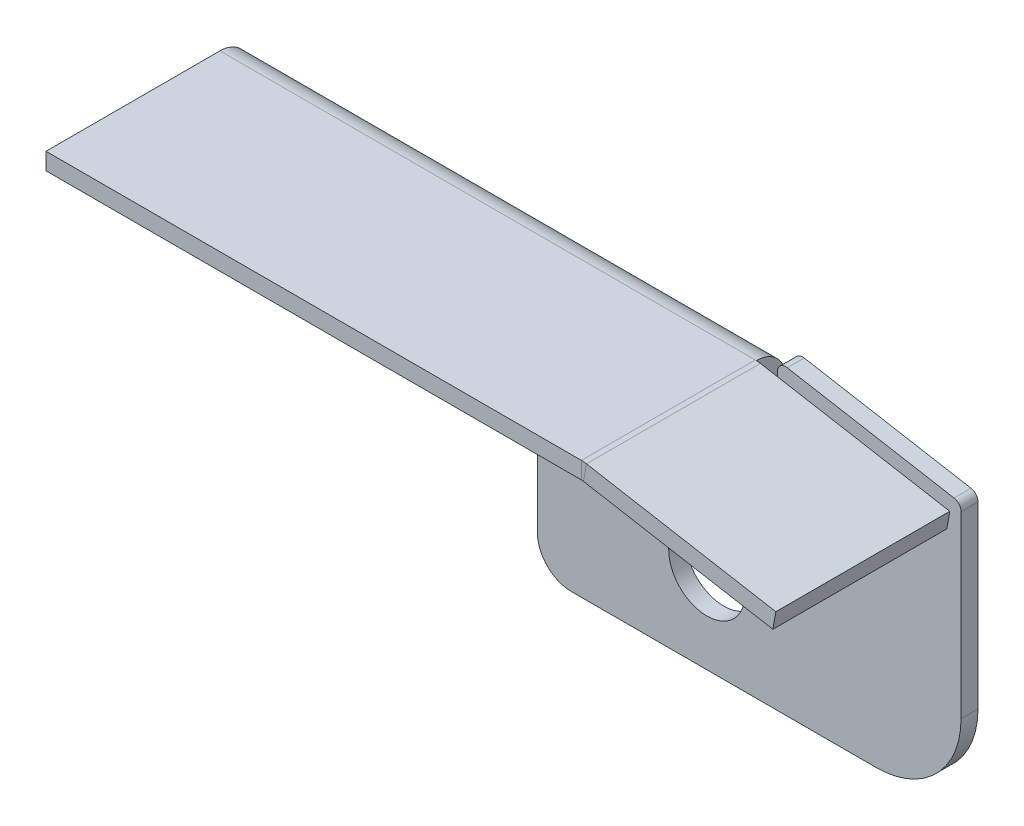
SolidWorks part; units mm, degrees
note: The reader was unsure of these and kept them because the rebuilt part matched: flange length of "Kante-Lasche1", "Kante-Lasche2".
material "1.4301 (X5CrNi18-10)"
ref_plane "Ebene vorne" through (0, 0, 0) normal (0, 0, 1) x (1, 0, 0)
ref_plane "Ebene oben" through (0, 0, 0) normal (0, 1, 0) x (1, 0, 0)
ref_plane "Ebene rechts" through (0, 0, 0) normal (1, 0, 0) x (0, 0, -1)
sketch "Skizze1" plane through (0, 0, 0) normal (0, 0, 1) x (1, 0, 0)
  line L0 (-42, -8.5) -> (-42, -16.5)
  line L1 (-40, -18.5) -> (-22, -18.5)
  line L2 (-17, -13.5) -> (-17, -2.5)
  line L3 (-17, -2.5) -> (-28.3426, -0.5)
  line L4 (-28.3426, -0.5) -> (-60, -0.5)
  line L5 (-42, 58) -> (-42, -58) construction
  line L6 (-32, -7.5) -> (-32, -13.5) construction
  line L7 (-29.75, -7.5) -> (-29.75, -13.5)
  line L8 (-34.25, -7.5) -> (-34.25, -13.5)
  line L9 (-42, -8.5) -> (-58, -8.5)
  line L10 (-60, 53) -> (-60, -53) construction
  line L12 (-60, 50) -> (-60, -50) construction
  line L13 (-60, -6.5) -> (-60, -0.5)
  arc A0 (-29.75, -7.5) -> (-34.25, -7.5) centre (-32, -7.5) ccw
  arc A1 (-34.25, -13.5) -> (-29.75, -13.5) centre (-32, -13.5) ccw
  arc A2 (-17, -13.5) -> (-22, -18.5) centre (-22, -13.5) cw
  arc A3 (-42, -16.5) -> (-40, -18.5) centre (-40, -16.5) ccw
  arc A4 (-58, -8.5) -> (-60, -6.5) centre (-58, -6.5) cw
  point P7 (-32, -10.5)
  point P26 (-17, -18.5)
  point P31 (-60, -8.5)
  dimension "D10" = 5
  dimension "D11" = 2
  dimension "D12" = 2
  dimension "D1" = 18
  dimension "D2" = 25
  dimension "D3" = 100
  dimension "D4" = 0.5
  dimension "D5" = 16
  dimension "D6" = 4.5
  dimension "D7" = 6
  dimension "D8" = 8
  dimension "D9" = 8
base flange "Basis-Blech1" sketch "Skizze1" thickness 1 reverse thickness direction yes parameters "D1"=0.7366
edge flange "Kante-Lasche1" sketch "Skizze11" flange angle 90 flange length 12 flange position material inside bend radius 0.7366 thickness 1 relief rectangular parameters "D6"=10, "D8"=1
sketch "Skizze11" plane through (0, -0.5, 1) normal (0, 1, 0) x (-1, 0, 0)
  line L2 (28.3426, 0) -> (28.3426, 11)
  line L3 (28.3426, 11) -> (60, 11)
  line L4 (60, 11) -> (60, 0)
  line L7 (28.3426, 0) -> (60, 0) construction
  line L8 (28.3426, 0) -> (60, 0)
bend "Kantenbiegung1" bend radius 0.7366 bend angle 90 parameters "D5"=1
edge flange "Kante-Lasche2" sketch "Skizze15" flange angle 170 flange length 11.5 flange position material outside bend radius 0.7366 thickness 1 relief none parameters "D6"=10
sketch "Skizze15" plane through (-28.3426, -1.5, 0) normal (0.1736, 0.9848, 0) x (0, 0, 1)
  line L2 (1.7366, 0) -> (1.7366, 11.4125)
  line L3 (1.7366, 11.4125) -> (12, 11.4125)
  line L4 (12, 11.4125) -> (12, 0)
  line L27 (12, 0) -> (1.7366, 0) construction
  line L28 (12, 0) -> (1.7366, 0)
bend "Kantenbiegung3" bend radius 0.7366 bend angle 10 parameters "D5"=2
fillet "Verrundung1" radius 0.5 2 edges at (-17, -2.5, 0.5) (-27.8426, -0.5882, 0.5)
sketch "Biegung-Linien1" [suppressed] plane through (0, 0, 0) normal (0, 1, 0) x (1, 0, 0)
sketch "Rahmen1" [suppressed] plane through (0, 0, 0) normal (0, 1, 0) x (1, 0, 0)
sheet metal parameters "Blech2" thickness 1 parameters "D1"=0.7366
flat pattern "Abwicklung2" [suppressed]
sketch "Biegung-Linien2" plane through (0, 0, 0) normal (0, 1, 0) x (1, 0, 0)
sketch3d "Rahmen2" [suppressed]
  line L0 (-42, -20, 0) -> (-17, -20, 0) construction
  line L1 (-42, -2, 0) -> (-17, -2, 0) construction
  line L2 (-42, -20, 0) -> (-42, -2, 0) construction
  line L3 (-17, -20, 0) -> (-17, -2, 0) construction
sheet metal parameters "Blech3" thickness 1 parameters "D1"=0.7366
flat pattern "Abwicklung2"
sketch "Biegung-Linien2" plane through (0, 0, 0) normal (0, 0, -1) x (-1, 0, 0)
  line L1 (42, -1.7654) -> (28.3426, -1.7654) construction
  line L3 (42, -1.7654) -> (28.3426, -1.7654) construction
sketch3d "Rahmen2" [suppressed]
  line L0 (17, 9.4692, 0) -> (17, -20, 0) construction
  line L1 (42, 9.4692, 0) -> (42, -20, 0) construction
  line L2 (17, 9.4692, 0) -> (42, 9.4692, 0) construction
  line L3 (17, -20, 0) -> (42, -20, 0) construction
bend of the flat pattern "Abwickeln-<Kantenbiegung1>1"
sheet metal parameters "Blech4" thickness 1 parameters "D1"=0.7366
flat pattern "Abwicklung2"
sketch "Biegung-Linien2" plane through (0, 0, 0) normal (0, 0, -1) x (-1, 0, 0)
  line L1 (42, -1.7654) -> (28.3426, -1.7654) construction
  line L3 (42, -1.7654) -> (28.3426, -1.7654) construction
sketch3d "Rahmen2" [suppressed]
  line L0 (17, 9.4692, 0) -> (17, -20, 0) construction
  line L1 (42, 9.4692, 0) -> (42, -20, 0) construction
  line L2 (17, 9.4692, 0) -> (42, 9.4692, 0) construction
  line L3 (17, -20, 0) -> (42, -20, 0) construction
bend of the flat pattern "Abwickeln-<Kantenbiegung1>1"
bend of the flat pattern "Abwickeln-<Kantenbiegung3>1"
